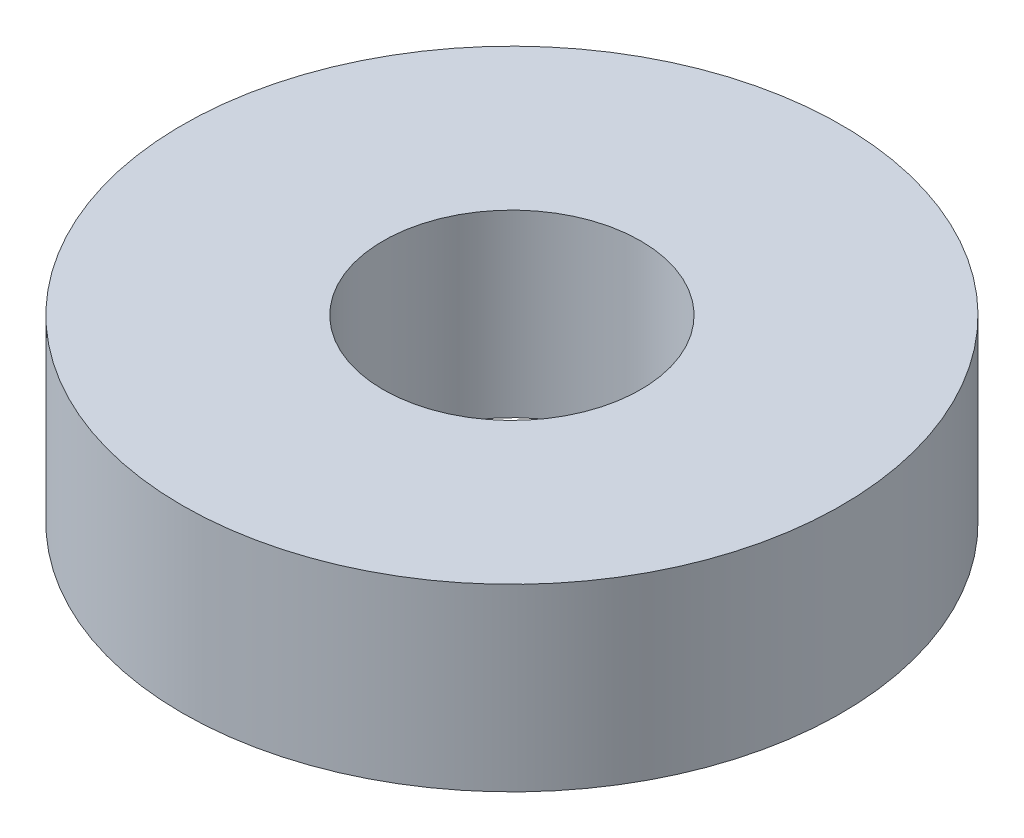
SolidWorks part; units mm, degrees
material "Onyx w/ CF"
ref_plane "Front Plane" through (0, 0, 0) normal (0, 0, 1) x (1, 0, 0)
ref_plane "Top Plane" through (0, 0, 0) normal (0, 1, 0) x (1, 0, 0)
ref_plane "Right Plane" through (0, 0, 0) normal (1, 0, 0) x (0, 0, -1)
sketch "Sketch1" plane through (0, 0, 0) normal (0, 1, 0) x (1, 0, 0)
  circle A0 centre (0, 0) radius 5.5
  dimension "D1" = 11
extrude "Boss-Extrude1" add sketch "Sketch1" along normal blind 3
hole_wizard "M4 Clearance Hole1" positions "Sketch2" profile "Sketch3" hole size "M4" standard "ANSI Metric" end condition up to next
sketch "Sketch2" plane through (0, 3, 0) normal (0, 1, 0) x (1, 0, 0)
  point P0 (0, 0)
sketch "Sketch3" plane through (0, 3, 0) normal (1, 0, 0) x (0, 0, 1)
  line L0 (0, 0) -> (0, 3)
  line L1 (0, 3) -> (2.15, 3)
  line L2 (2.15, 3) -> (2.15, 0)
  line L5 (2.15, 0) -> (0, 0)
  line L11 (0, -6.35) -> (0, 107.95) construction
  dimension "Thru Hole Dia." = 4.3
  dimension "Thru Hole Depth" = 3
sketch "Sketch5" plane through (0, 0, 0) normal (0, -1, 0) x (1, 0, 0)
  line L0 (2.7003, 4.677) -> (-2.7003, 4.677) construction
  line L1 (2.6269, -4.55) -> (5.2539, 0) construction
  line L2 (5.2539, 0) -> (2.6269, 4.55) construction
  line L3 (2.6269, 4.55) -> (-2.6269, 4.55) construction
  line L4 (-2.6269, 4.55) -> (-5.2539, 0) construction
  line L5 (-5.2539, 0) -> (-2.6269, -4.55) construction
  line L6 (-2.6269, -4.55) -> (2.6269, -4.55) construction
  line L7 (-2.7003, 4.677) -> (-5.4005, 0) construction
  line L8 (-5.4005, 0) -> (-2.7003, -4.677) construction
  line L9 (-2.7003, -4.677) -> (2.7003, -4.677) construction
  line L10 (2.7003, -4.677) -> (5.4005, 0) construction
  line L11 (5.4005, 0) -> (2.7003, 4.677) construction
  line L12 (1.9763, 3.423) -> (-1.9763, 3.423) construction
  line L13 (-1.9763, 3.423) -> (-3.9525, 0) construction
  line L14 (-3.9525, 0) -> (-1.9763, -3.423) construction
  line L15 (-1.9763, -3.423) -> (1.9763, -3.423) construction
  line L16 (1.9763, -3.423) -> (3.9525, 0) construction
  line L17 (3.9525, 0) -> (1.9763, 3.423) construction
  line L18 (-2.7003, 4.677) -> (-2.7003, 3.423) construction
  line L19 (-2.7003, 3.423) -> (2.7003, 3.423) construction
  line L20 (2.7003, 3.423) -> (2.7003, 4.677) construction
  line L21 (-3.9525, 0) -> (3.9525, 0) construction
  line L22 (-2.7003, -4.677) -> (2.7003, -4.677) construction
  line L23 (-2.7003, -4.677) -> (-2.7003, -3.423) construction
  line L24 (-2.7003, -3.423) -> (2.7003, -3.423) construction
  line L25 (2.7003, -4.677) -> (2.7003, -3.423) construction
  line L26 (-1.627, 3.423) -> (1.627, 3.423)
  line L27 (-1.627, 3.423) -> (-1.627, 4.677)
  line L28 (-1.627, 4.677) -> (1.627, 4.677)
  line L29 (1.627, 3.423) -> (1.627, 4.677)
  line L30 (-1.627, -4.677) -> (1.627, -4.677)
  line L31 (1.627, -3.423) -> (1.627, -4.677)
  line L32 (-1.627, -3.423) -> (1.627, -3.423)
  line L33 (-1.627, -3.423) -> (-1.627, -4.677)
  circle A0 centre (0, 0) radius 4.55 construction
  point P1 (0, 4.55)
  point P31 (0, 3.423)
  dimension "D1" = 9.1
  dimension "D4" = 3.254
  dimension "D2" = 0.127
  dimension "D3" = 1.254
extrude "Cut-Extrude2" cut sketch "Sketch5" against normal blind 2 contours L9 L25 L24 L23 | L19 L20 L0 L18 | L26 L29 L28 L27 | L32 L33 L30 L31 region at (0, 0, 4.05) region at (0, 0, -4.05)
